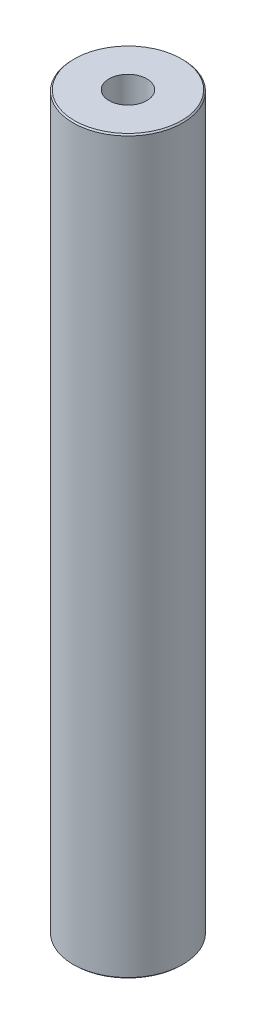
SolidWorks part; units mm, degrees
ref_plane "Front Plane" through (0, 0, 0) normal (0, 0, 1) x (1, 0, 0)
ref_plane "Top Plane" through (0, 0, 0) normal (0, 1, 0) x (1, 0, 0)
ref_plane "Right Plane" through (0, 0, 0) normal (1, 0, 0) x (0, 0, -1)
sketch "Sketch1" plane through (0, 0, 0) normal (0, 1, 0) x (1, 0, 0)
  circle A0 centre (0, 0) radius 45
  dimension "SHAFT_OD" = 90
extrude "Boss-Extrude1" add sketch "Sketch1" along normal blind 600
sketch "Sketch2" plane through (0, 0, 0) normal (0, 1, 0) x (1, 0, 0)
  circle A0 centre (0, 0) radius 15.5059
  dimension "BORE_D" = 31.0117
extrude "Cut-Extrude1" cut sketch "Sketch2" along normal through all
chamfer "Chamfer1" distance 1.0711 angle 45 2 edges at (0, 600, 45) (0, 0, 45)
